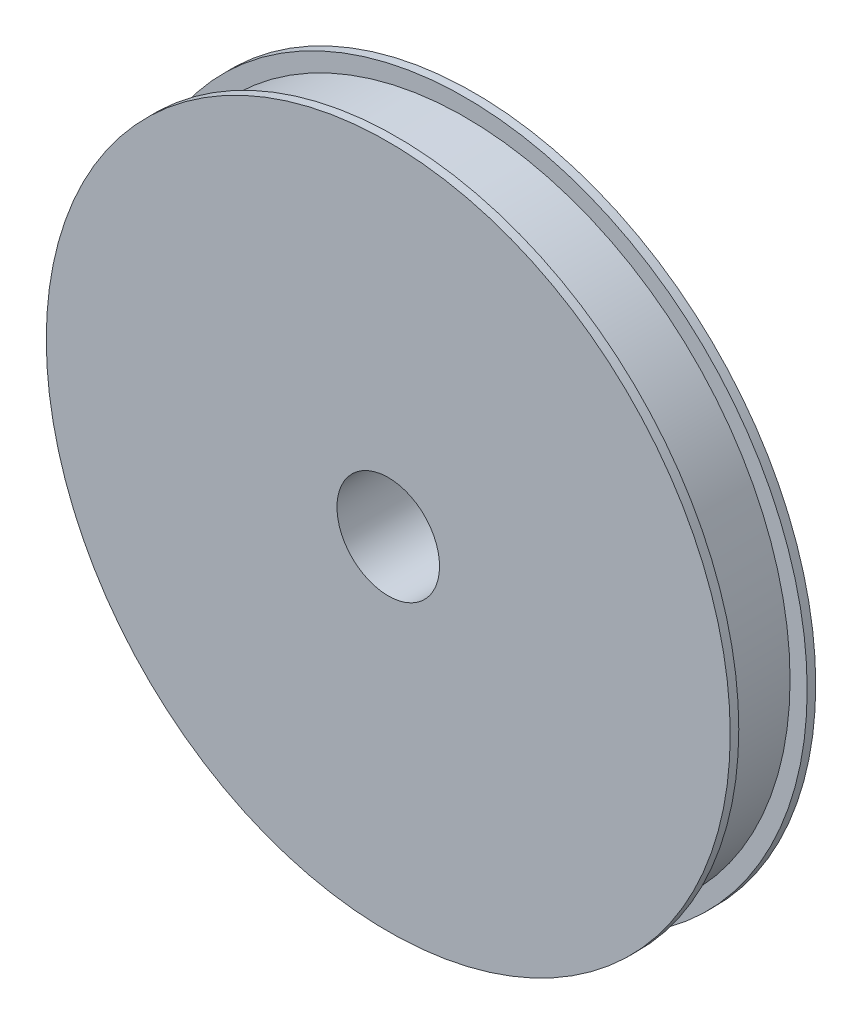
SolidWorks part; units mm, degrees
material "1023 Carbon Steel Sheet (SS)"
ref_plane "Front Plane" through (0, 0, 0) normal (0, 0, 1) x (1, 0, 0)
ref_plane "Top Plane" through (0, 0, 0) normal (0, 1, 0) x (1, 0, 0)
ref_plane "Right Plane" through (0, 0, 0) normal (1, 0, 0) x (0, 0, -1)
sketch "Sketch1" plane through (0, 0, 0) normal (0, 0, 1) x (1, 0, 0)
  circle A0 centre (0, 0) radius 40
  circle A1 centre (0, 0) radius 6
  circle A2 centre (0, 0) radius 38
  dimension "D1" = 12
  dimension "D2" = 80
  dimension "D3" = 76
extrude "Boss-Extrude1" add sketch "Sketch1" along normal blind 10 contours A2 A1 | A0 A2 region at (-38.8686, 0, 0) region at (-36.9252, 0, 0)
extrude "Cut-Extrude1" cut sketch "Sketch1<3>" along normal blind 8 from offset 1 contours A0 A2 region at (-38.8686, 0, 0)
sketch "Sketch1<3>" plane through (0, 0, 0) normal (0, 0, 1) x (1, 0, 0) same geometry as "Sketch1"
